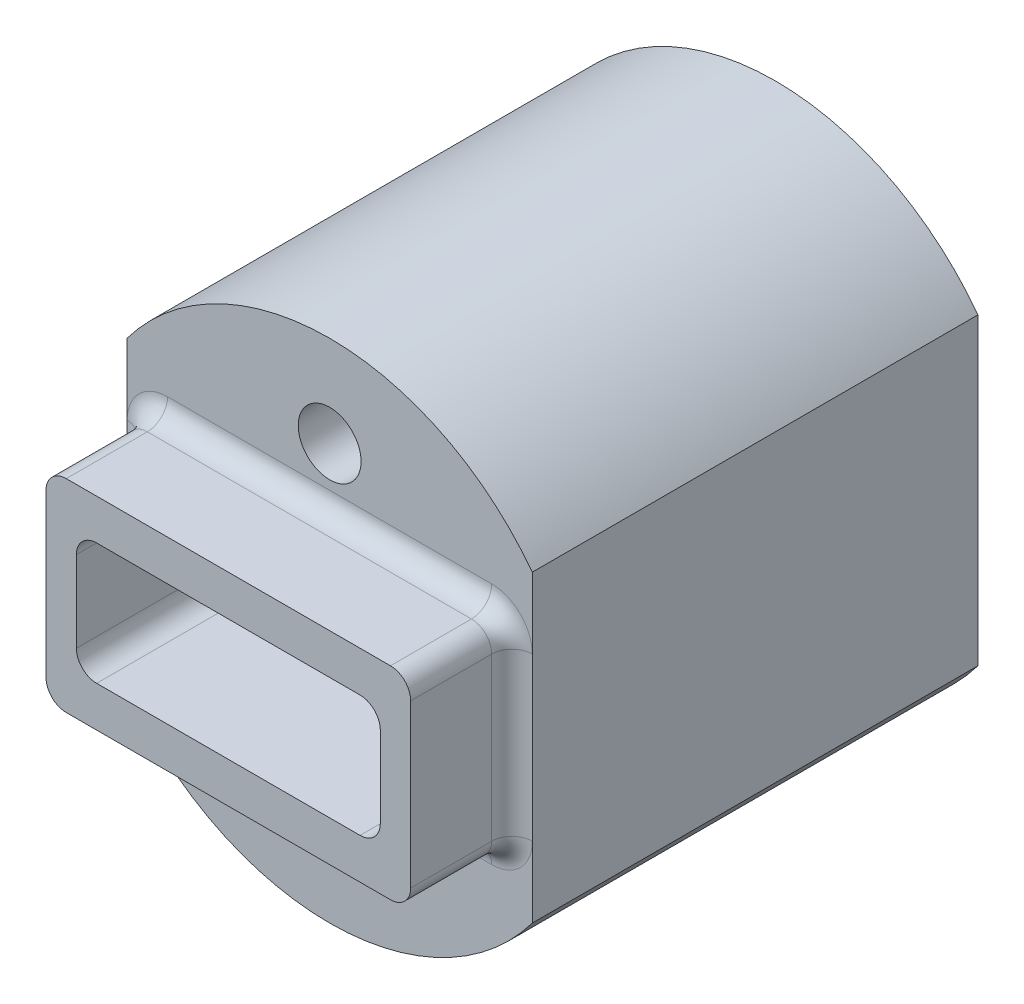
SolidWorks part; units mm, degrees
ref_plane "Ebene vorne" through (0, 0, 0) normal (0, 0, 1) x (1, 0, 0)
ref_plane "Ebene oben" through (0, 0, 0) normal (0, 1, 0) x (1, 0, 0)
ref_plane "Ebene rechts" through (0, 0, 0) normal (1, 0, 0) x (0, 0, -1)
sketch "Skizze1" plane through (0, 0, 0) normal (0, 0, 1) x (1, 0, 0)
  line L0 (0, 26.6232) -> (0, -18.9292) construction
  line L1 (-23.6459, 0) -> (19.5794, 0) construction
  circle A0 centre (0, 0) radius 12.5
  circle A1 centre (0, 8) radius 1.55
  circle A2 centre (0, -8) radius 1.55
  dimension "D1" = 25
  dimension "D2" = 3.1
  dimension "D3" = 16
extrude "Aufsatz-Linear austragen1" add sketch "Skizze1" along normal blind 7.5 and the other way blind 14.5
sketch "Skizze2" plane through (0, 0, -14.5) normal (0, 0, -1) x (-1, 0, 0)
  line L0 (-20.9915, 0) -> (20.1572, 0) construction
  line L1 (0, 18.5911) -> (0, -18.5544) construction
  line L2 (-9, -4) -> (-9, 4)
  line L3 (-8, 5) -> (8, 5)
  line L4 (-8, -5) -> (8, -5)
  line L5 (9, -4) -> (9, 4)
  arc A0 (-8, 5) -> (-9, 4) centre (-8, 4) ccw
  arc A1 (-8, -5) -> (-9, -4) centre (-8, -4) cw
  arc A2 (8, -5) -> (9, -4) centre (8, -4) ccw
  arc A3 (8, 5) -> (9, 4) centre (8, 4) cw
  point P13 (0, 5)
  point P14 (-9, 0)
  point P20 (9, 0)
  point P21 (0, -5)
  dimension "D1" = 1
  dimension "D2" = 10
  dimension "D3" = 18
extrude "Schnitt-Linear austragen1" cut sketch "Skizze2" against normal blind 4.5
sketch "Skizze3" plane through (0, 0, 7.5) normal (0, 0, 1) x (1, 0, 0)
  line L0 (18.7113, 0) -> (-15.5181, 0) construction
  line L1 (0, 15.8588) -> (0, -16.495) construction
  line L2 (-8, 5) -> (8, 5)
  line L3 (9, 4) -> (9, -4)
  line L4 (-8, -5) -> (8, -5)
  line L5 (-9, 4) -> (-9, -4)
  arc A0 (8, 5) -> (9, 4) centre (8, 4) cw
  arc A1 (8, -5) -> (9, -4) centre (8, -4) ccw
  arc A2 (-8, -5) -> (-9, -4) centre (-8, -4) cw
  arc A3 (-8, 5) -> (-9, 4) centre (-8, 4) ccw
  point P8 (0, 5)
  point P13 (9, 0)
  point P20 (-9, 0)
  point P21 (0, -5)
  dimension "D1" = 1
  dimension "D2" = 18
  dimension "D3" = 10
extrude "Aufsatz-Linear austragen2" add sketch "Skizze3" along normal blind 5
sketch "Skizze4" plane through (0, 0, 0) normal (0, 0, 1) x (1, 0, 0)
  line L0 (23.0396, 0) -> (-15.6217, 0) construction
  line L1 (0, -18.7774) -> (0, 16.1377) construction
  line L2 (-6.5, -3) -> (6.5, -3)
  line L3 (7.5, -2) -> (7.5, 2)
  line L4 (-7.5, -2) -> (-7.5, 2)
  line L5 (-6.5, 3) -> (6.5, 3)
  arc A0 (6.5, -3) -> (7.5, -2) centre (6.5, -2) ccw
  arc A1 (-6.5, -3) -> (-7.5, -2) centre (-6.5, -2) cw
  arc A2 (-6.5, 3) -> (-7.5, 2) centre (-6.5, 2) ccw
  arc A3 (6.5, 3) -> (7.5, 2) centre (6.5, 2) cw
  point P13 (7.5, 0)
  point P14 (0, -3)
  point P20 (0, 3)
  point P21 (-7.5, 0)
  dimension "D1" = 1
  dimension "D2" = 15
  dimension "D3" = 6
extrude "Schnitt-Linear austragen4" cut sketch "Skizze4" against normal through all and the other way through all
ref_axis "Achse1" through (0, 0, 13.85) along (0, 0, -1)
sketch "Skizze5" plane through (0, 0, 0) normal (0, 0, 1) x (1, 0, 0)
  line L0 (0, 18.6124) -> (0, -19.0354) construction
  line L1 (18.2952, 0) -> (-19.1412, 0) construction
  line L2 (10, 15) -> (10, -15)
  line L3 (10, 15) -> (-10, 15)
  line L4 (10, -15) -> (-10, -15)
  line L5 (-10, 15) -> (-10, -15)
  point P9 (10, 0)
  point P10 (-10, 0)
  point P12 (0, -15)
  point P13 (0, 15)
  dimension "D1" = 20
  dimension "D2" = 30
extrude "Schnitt-Linear austragen5" cut sketch "Skizze5" against normal through all and the other way blind 10 flip side to cut
fillet "Verrundung1" radius 1.2 8 edges at (-8.7071, 4.7071, -14.5) (-8.7071, -4.7071, -14.5) (0, -5, -14.5) (8.7071, -4.7071, -14.5) (8.7071, 4.7071, -14.5) (0, 5, -14.5) (-9, 0, -14.5) (9, 0, -14.5)
fillet "Verrundung2" radius 1 8 edges at (8.7071, 4.7071, 7.5) (9, 0, 7.5) (8.7071, -4.7071, 7.5) (0, -5, 7.5) (-8.7071, -4.7071, 7.5) (-9, 0, 7.5) (-8.7071, 4.7071, 7.5) (0, 5, 7.5)
